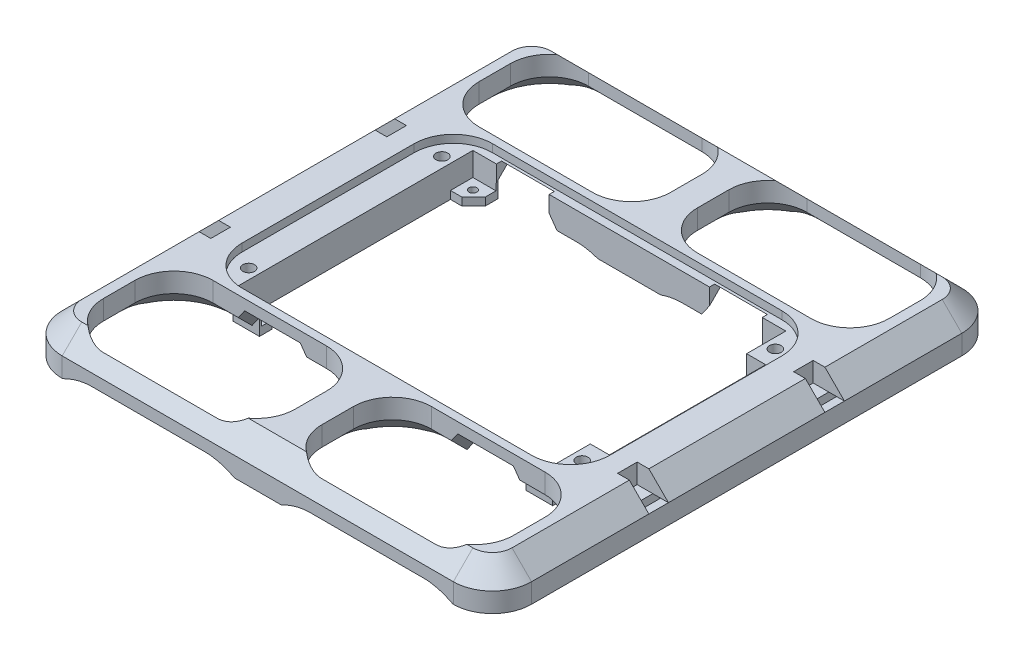
SolidWorks part; units mm, degrees
ref_plane "Front Plane" through (0, 0, 0) normal (0, 0, 1) x (1, 0, 0)
ref_plane "Top Plane" through (0, 0, 0) normal (0, 1, 0) x (1, 0, 0)
ref_plane "Right Plane" through (0, 0, 0) normal (1, 0, 0) x (0, 0, -1)
sketch "Sketch1" plane through (0, 0, 0) normal (0, 1, 0) x (1, 0, 0)
  line L1 (-51.9884, 11.9013) -> (68.0116, 11.9013)
  line L2 (-51.9884, 11.9013) -> (-51.9884, -118.0987)
  line L3 (-51.9884, -118.0987) -> (68.0116, -118.0987)
  line L4 (68.0116, 11.9013) -> (68.0116, -118.0987)
  dimension "D1" = 120
  dimension "D2" = 130
extrude "Boss-Extrude1" add sketch "Sketch1" along normal blind 10
fillet "Fillet2" radius 10 4 edges at (-51.9884, 5, -11.9013) (-51.9884, 5, 118.0987) (68.0116, 5, 118.0987) (68.0116, 5, -11.9013) first distance on face at (-51.9884, 5, 53.0987) first distance on face at (68.0116, 5, 53.0987)
sketch "Sketch5" plane through (0, 10, 0) normal (0, 1, 0) x (1, 0, 0)
  line L0 (-41.9884, -118.0987) -> (58.0116, -118.0987) construction
  line L1 (-44.4241, -115.0987) -> (4.5797, -115.0987)
  line L2 (-44.4241, -115.0987) -> (-44.4241, -87.0987)
  line L3 (-44.4241, -87.0987) -> (4.5797, -87.0987)
  line L4 (4.5797, -115.0987) -> (4.5797, -87.0987)
  point P4 (4.5797, -101.0987)
  dimension "D1" = 28
  dimension "D2" = 17
extrude "Cut-Extrude3" cut sketch "Sketch5" against normal up to next
ref_plane "Plane1" through (8.0116, 0, 0) normal (-1, 0, 0) x (0, 0, 1)
ref_plane "Plane2" through (0, 0, 53.0987) normal (0, 0, -1) x (-1, 0, 0)
mirror "Mirror1" about plane through (8.0116, 0, 0) normal (-1, 0, 0) of "Cut-Extrude3"
mirror "Mirror2" about plane through (0, 0, 53.0987) normal (0, 0, -1) of "Mirror1"
fillet "Fillet3" radius 10 16 edges at (60.4472, 5, -8.9013) (60.4472, 5, 19.0987) (11.4435, 5, -8.9013) (11.4435, 5, 19.0987) (4.5797, 5, -8.9013) (4.5797, 5, 19.0987) (-44.4241, 5, -8.9013) (-44.4241, 5, 19.0987) (-44.4241, 5, 87.0987) (11.4435, 5, 87.0987) (60.4472, 5, 87.0987) (4.5797, 5, 87.0987) (-44.4241, 5, 115.0987) (4.5797, 5, 115.0987) (11.4435, 5, 115.0987) (60.4472, 5, 115.0987) first distance on face at (60.4472, 5, 5.0987) first distance on face at (35.9453, 5, 19.0987) first distance on face at (35.9453, 5, -8.9013) first distance on face at (11.4435, 5, 5.0987) first distance on face at (4.5797, 5, 5.0987) first distance on face at (-19.9222, 5, 19.0987) first distance on face at (-19.9222, 5, -8.9013) first distance on face at (-44.4241, 5, 5.0987) first distance on face at (-19.9222, 5, 87.0987) first distance on face at (35.9453, 5, 87.0987) first distance on face at (4.5797, 5, 101.0987) first distance on face at (-44.4241, 5, 101.0987) first distance on face at (-19.9222, 5, 115.0987) first distance on face at (35.9453, 5, 115.0987)
chamfer "Chamfer6" distance 5 angle 45 32 edges at (11.4435, 0, 101.0987) (13.6348, 0, 111.3456) (15.1965, 0, 89.29) (35.9453, 0, 115.0987) (35.9453, 0, 87.0987) (56.6941, 0, 112.9074) (58.2559, 0, 90.8518) (60.4472, 0, 101.0987) (-44.4241, 0, 101.0987) (-40.671, 0, 89.29) (-42.2328, 0, 111.3456) (-19.9222, 0, 87.0987) (-19.9222, 0, 115.0987) (2.3884, 0, 90.8518) (0.8266, 0, 112.9074) (4.5797, 0, 101.0987) (11.4435, 0, 5.0987) (15.1965, 0, -6.71) (13.6348, 0, 15.3456) (35.9453, 0, -8.9013) (35.9453, 0, 19.0987) (58.2559, 0, -5.1482) (56.6941, 0, 16.9074) (60.4472, 0, 5.0987) (-44.4241, 0, 5.0987) (-42.2328, 0, 15.3456) (-40.671, 0, -6.71) (-19.9222, 0, 19.0987) (-19.9222, 0, -8.9013) (0.8266, 0, 16.9074) (2.3884, 0, -5.1482) (4.5797, 0, 5.0987)
sketch "Sketch6" plane through (0, 10, 0) normal (0, 1, 0) x (1, 0, 0)
  line L0 (68.0116, -108.0987) -> (68.0116, 1.9013) construction
  line L1 (48.0116, -83.0987) -> (-31.9884, -83.0987)
  line L2 (48.0116, -83.0987) -> (48.0116, -23.0987)
  line L3 (48.0116, -23.0987) -> (-31.9884, -23.0987)
  line L4 (-31.9884, -83.0987) -> (-31.9884, -23.0987)
  line L5 (-41.9884, -118.0987) -> (58.0116, -118.0987) construction
  point P4 (48.0116, -53.0987)
  point P7 (68.0116, -53.0987)
  point P8 (8.0116, -83.0987)
  point P11 (8.0116, -118.0987)
  dimension "D1" = 80
  dimension "D2" = 60
  dimension "D3" = 0
  dimension "D4" = 0
extrude "Cut-Extrude4" cut sketch "Sketch6" against normal up to next
chamfer "Chamfer7" distance 5 angle 45 8 edges at (-51.9884, 10, 53.0987) (-49.7971, 10, 114.3456) (-48.2354, 10, -9.71) (8.0116, 10, 118.0987) (8.0116, 10, -11.9013) (64.2585, 10, 115.9074) (65.8203, 10, -8.1482) (68.0116, 10, 53.0987)
sketch "Sketch7" plane through (0, 10, 0) normal (0, 1, 0) x (1, 0, 0)
  line L20 (-33.9884, -85.0987) -> (50.0116, -85.0987)
  line L21 (50.0116, -85.0987) -> (50.0116, -21.0987)
  line L22 (-33.9884, -21.0987) -> (-33.9884, -85.0987)
  line L23 (50.0116, -21.0987) -> (-33.9884, -21.0987)
  line L24 (-33.9884, -85.0987) -> (50.0116, -85.0987)
  line L25 (50.0116, -85.0987) -> (50.0116, -21.0987)
  line L26 (-33.9884, -21.0987) -> (-33.9884, -85.0987)
  line L27 (50.0116, -21.0987) -> (-33.9884, -21.0987)
  dimension "D1" = 2
extrude "Cut-Extrude5" cut sketch "Sketch7" against normal blind 2
sketch "Sketch10" plane through (0, 10, 0) normal (0, 1, 0) x (1, 0, 0)
  line L1 (50.0116, -21.0987) -> (55.0116, -21.0987)
  line L2 (50.0116, -21.0987) -> (50.0116, -85.0987)
  line L3 (50.0116, -85.0987) -> (55.0116, -85.0987)
  line L4 (55.0116, -21.0987) -> (55.0116, -85.0987)
  dimension "D1" = 5
extrude "Cut-Extrude6" cut sketch "Sketch10" against normal blind 2
fillet "Fillet4" radius 10 2 edges at (55.0116, 9, 85.0987) (55.0116, 9, 21.0987) first distance on face at (55.0116, 9, 53.0987)
mirror "Mirror3" about plane through (8.0116, 0, 0) normal (-1, 0, 0) of "Cut-Extrude6", "Fillet4"
sketch "Sketch11" plane through (0, 8, 0) normal (0, 1, 0) x (1, 0, 0)
  line L0 (48.0116, -23.0987) -> (48.0116, -83.0987) construction
  line L1 (48.0116, -73.0806) -> (52.8889, -73.0806)
  line L2 (48.0116, -73.0806) -> (48.0116, -33.1167)
  line L3 (48.0116, -33.1167) -> (52.8889, -33.1167)
  line L4 (52.8889, -73.0806) -> (52.8889, -33.1167)
  point P6 (48.0116, -53.0987)
  point P7 (48.0116, -53.0987)
  dimension "D1" = 0
extrude "Cut-Extrude7" cut sketch "Sketch11" against normal blind 10
sketch "Sketch12" plane through (0, 0, 0) normal (0, -1, 0) x (-1, 0, 0)
  line L0 (2.7528, -53.0987) -> (-2.7528, -53.0987) construction
  line L1 (-66.0116, -98.0987) -> (-64.0116, -98.0987)
  line L2 (-66.0116, -98.0987) -> (-66.0116, -8.0987)
  line L3 (-66.0116, -8.0987) -> (-64.0116, -8.0987)
  line L4 (-64.0116, -98.0987) -> (-64.0116, -8.0987)
  line L5 (-68.0116, -108.0987) -> (-68.0116, 1.9013) construction
  point P4 (-64.0116, -53.0987)
  dimension "D1" = 0
  dimension "D2" = 2
  dimension "D3" = 2
  dimension "D4" = 90
extrude "Cut-Extrude8" cut sketch "Sketch12" against normal blind 5
mirror "Mirror4" about plane through (8.0116, 0, 0) normal (-1, 0, 0) of "Cut-Extrude8"
sketch "Sketch13" plane through (0, 8, 0) normal (0, 1, 0) x (1, 0, 0)
  circle A0 centre (50.6334, -28.397) radius 1.5
  dimension "D1" = 3
extrude "Cut-Extrude9" cut sketch "Sketch13" against normal blind 3
mirror "Mirror5" about plane through (8.0116, 0, 0) normal (-1, 0, 0) of "Cut-Extrude9"
mirror "Mirror6" about plane through (0, 0, 53.0987) normal (0, 0, -1) of "Mirror5"
sketch "Sketch14" plane through (0, 0, 0) normal (0, -1, 0) x (-1, 0, 0)
  line L1 (-48.9094, -77.3641) -> (-42.1015, -77.3641)
  line L2 (-48.9094, -77.3641) -> (-48.9094, -83.5788)
  line L3 (-48.9094, -83.5788) -> (-42.1015, -83.5788)
  line L4 (-42.1015, -77.3641) -> (-42.1015, -83.5788)
extrude "Boss-Extrude2" add sketch "Sketch14" against normal blind 2
sketch "Sketch15" plane through (0, 0, 0) normal (0, -1, 0) x (-1, 0, 0)
  circle A0 centre (-45.2516, -80.3408) radius 1
extrude "Cut-Extrude10" cut sketch "Sketch15" against normal blind 2
mirror "Mirror7" about plane through (0, 0, 53.0987) normal (0, 0, -1) of "Cut-Extrude10", "Boss-Extrude2"
mirror "Mirror8" about plane through (8.0116, 0, 0) normal (-1, 0, 0) of "Mirror7"
chamfer "Chamfer8" distance 3 angle 45 4 edges at (-26.0784, 1, 28.8333) (42.1015, 1, 28.8333) (-26.0784, 1, 77.3641) (42.1015, 1, 77.3641)
sketch "Sketch16" plane through (0, 12.0493, 12.0493) normal (0, -0.7071, -0.7071) x (-1, 0, 0)
  line L1 (25.9721, -16.3337) -> (12.4884, -16.3337)
  line L2 (25.9721, -16.3337) -> (25.9721, -9.7477)
  line L3 (25.9721, -9.7477) -> (12.4884, -9.7477)
  line L4 (12.4884, -16.3337) -> (12.4884, -9.7477)
extrude "Cut-Extrude11" cut sketch "Sketch16" against normal blind 10
mirror "Mirror9" about plane through (8.0116, 0, 0) normal (-1, 0, 0) of "Cut-Extrude11"
mirror "Mirror10" about plane through (0, 0, 53.0987) normal (0, 0, -1) of "Mirror9"
chamfer "Chamfer9" distance 2 angle 45 8 edges at (41.9952, 3, 85.0987) (28.5115, 3, 85.0987) (-12.4884, 3, 85.0987) (-25.9721, 3, 85.0987) (41.9952, 3, 21.0987) (28.5115, 3, 21.0987) (-12.4884, 3, 21.0987) (-25.9721, 3, 21.0987)
chamfer "Chamfer10" distance 2 angle 45 4 edges at (35.2533, 5.3134, 87.0987) (35.2533, 5.3134, 19.0987) (-19.2302, 5.3134, 19.0987) (-19.2302, 5.3134, 87.0987) first distance on face at (34.8793, 6.3284, 87.0987) first distance on face at (36.3193, 6.3284, 19.0987) first distance on face at (-18.8562, 6.3284, 19.0987) first distance on face at (-20.2962, 6.3284, 87.0987)
sketch "Sketch17" plane through (0, 10, 0) normal (0, 1, 0) x (1, 0, 0)
  line L0 (63.0116, -108.0987) -> (63.0116, 1.9013) construction
  line L1 (60.0116, -78.0987) -> (74.9562, -78.0987)
  line L2 (60.0116, -78.0987) -> (60.0116, -73.0987)
  line L3 (60.0116, -73.0987) -> (74.9562, -73.0987)
  line L4 (74.9562, -78.0987) -> (74.9562, -73.0987)
  line L5 (2.7528, -53.0987) -> (-2.7528, -53.0987) construction
  dimension "D1" = 5
  dimension "D2" = 3
  dimension "D3" = 20
extrude "Cut-Extrude12" cut sketch "Sketch17" against normal blind 5
mirror "Mirror11" about plane through (0, 0, 53.0987) normal (0, 0, -1) of "Cut-Extrude12"
mirror "Mirror12" about plane through (8.0116, 0, 0) normal (-1, 0, 0) of "Mirror11"
